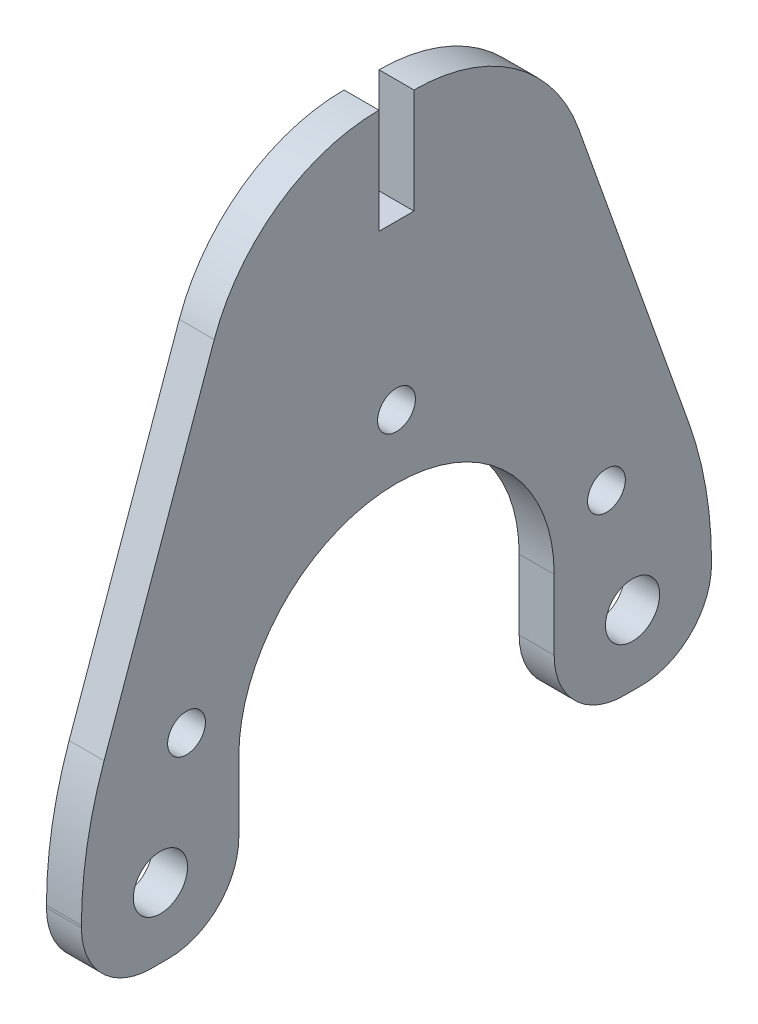
SolidWorks part; units mm, degrees
material "6061 Alloy"
ref_plane "Front Plane" through (0, 0, 0) normal (0, 0, 1) x (1, 0, 0)
ref_plane "Top Plane" through (0, 0, 0) normal (0, 1, 0) x (1, 0, 0)
ref_plane "Right Plane" through (0, 0, 0) normal (1, 0, 0) x (0, 0, -1)
sketch "Sketch1" plane through (0, 0, 0) normal (1, 0, 0) x (0, 0, -1)
  line L0 (1.5875, 44.45) -> (1.5875, 34.925)
  line L1 (1.5875, 34.925) -> (-1.5875, 34.925)
  line L2 (0, 0) -> (0, 73.524) construction
  line L3 (-1.5875, 44.45) -> (-1.5875, 34.925)
  line L4 (21.4566, -6.35) -> (-21.4566, -6.35) construction
  line L5 (16.5446, 33.895) -> (28.6004, 0)
  line L6 (-16.5446, 33.895) -> (-28.6004, 0)
  line L7 (28.6004, 0) -> (28.6004, -12.7)
  line L8 (28.6004, -12.7) -> (14.3129, -12.7)
  line L9 (14.3129, -12.7) -> (14.3129, 0)
  line L10 (-14.3129, 0) -> (-14.3129, -12.7)
  line L11 (-14.3129, -12.7) -> (-28.6004, -12.7)
  line L12 (-28.6004, -12.7) -> (-28.6004, 0)
  arc A0 (14.3129, 0) -> (-14.3129, 0) centre (0, 0) ccw
  arc A5 (16.5446, 33.895) -> (1.5875, 44.45) centre (1.5875, 28.575) ccw
  arc A10 (-16.5446, 33.895) -> (-1.5875, 44.45) centre (-1.5875, 28.575) cw
  circle A11 centre (21.4566, -6.35) radius 2.5797 construction
  circle A12 centre (-21.4566, -6.35) radius 2.5797 construction
  point P1 (0, -6.35)
  point P9 (21.4566, -12.7)
  point P18 (0, 34.925)
  dimension "D1" = 28.6258
  dimension "D3" = 57.15
  dimension "D4" = 15.875
  dimension "D5" = 12.7
  dimension "D6" = 42.9133
  dimension "D7" = 14.2875
  dimension "D9" = 5.1594
  dimension "D2" = 3.175
  dimension "D10" = 6.35
  dimension "D12" = 9.525
extrude "Boss-Extrude1" add sketch "Sketch1" along normal blind 3.175
hole_wizard "#10 (0.1935) Diameter Hole1" positions "Sketch2" profile "Sketch3" hole size "#10" standard "ANSI Inch"
sketch "Sketch2" plane through (0, 0, 0) normal (-1, 0, 0) x (0, 0, 1)
  line L2 (-21.4312, -6.35) -> (21.4312, -6.35) construction
  point P0 (-21.4312, -6.35)
  point P2 (21.4312, -6.35)
  point P29 (0, -6.35)
  dimension "D1" = 42.8625
  dimension "D2" = 6.35
sketch "Sketch3" plane through (0, -6.35, -21.4312) normal (0, 1, 0) x (0, 0, 1)
  line L0 (0, 0) -> (0, 20.4786)
  line L1 (0, 20.4786) -> (2.4574, 19.002)
  line L2 (2.4574, 19.002) -> (2.4574, 0)
  line L5 (2.4574, 0) -> (0, 0)
  line L10 (0, 20.4786) -> (-2.4574, 19.002) construction
  line L11 (0, -6.35) -> (0, 107.95) construction
  dimension "Hole Dia." = 4.9149
  dimension "Hole Depth" = 19.002
  dimension "Drill Angle" = 118
sketch "Sketch4" plane through (3.175, 0, 0) normal (1, 0, 0) x (0, 0, -1)
  circle A6 centre (0, 20.0978) radius 1.7145 construction
  circle A7 centre (0, 20.0978) radius 1.7145
  circle A8 centre (-19.0616, 4.2227) radius 1.7145 construction
  circle A9 centre (-19.0616, 4.2227) radius 1.7145
  circle A10 centre (19.0616, 4.2228) radius 1.7145 construction
  circle A11 centre (19.0616, 4.2228) radius 1.7145
extrude "Cut-Extrude1" cut sketch "Sketch4" against normal through all
fillet "Fillet2" radius 35.56 2 edges at (1.5875, 0, 28.6004) (1.5875, 0, -28.6004)
fillet "Fillet1" radius 6.35 4 edges at (1.5875, -12.7, -28.6004) (1.5875, -12.7, -14.3129) (1.5875, -12.7, 28.6004) (1.5875, -12.7, 14.3129)
sketch "Sketch5" [suppressed] plane through (3.175, 0, 0) normal (1, 0, 0) x (0, 0, -1)
  line L0 (-16.5481, 33.885) -> (-26.5267, 5.7708) construction
  line L1 (-4.7625, 44.1293) -> (-25.9843, 44.1293)
  line L2 (-25.9843, 44.1293) -> (-25.9843, 7.2993)
  line L3 (-1.5875, 34.925) -> (-1.5875, 44.45) construction
  line L4 (-4.7625, 44.1293) -> (-4.7625, 41.2634)
  line L5 (-1.5875, 34.925) -> (-1.5875, 44.45) construction
  arc A1 (-1.5875, 44.45) -> (-16.5481, 33.885) centre (-1.5875, 28.575) ccw construction
  arc A3 (-11.1125, 27.0644) -> (-25.9843, 7.2993) centre (31.2208, -20.2657) ccw
  arc A4 (-4.7625, 41.2634) -> (-11.1125, 27.0644) centre (-23.8125, 41.2634) cw
  dimension "D1" = 3.175
  dimension "D2" = 19.05
  dimension "D4" = 63.5
  dimension "D3" = 9.525
  dimension "D5" = 36.83
extrude "Cut-Extrude2" [suppressed] cut sketch "Sketch5" against normal through all
